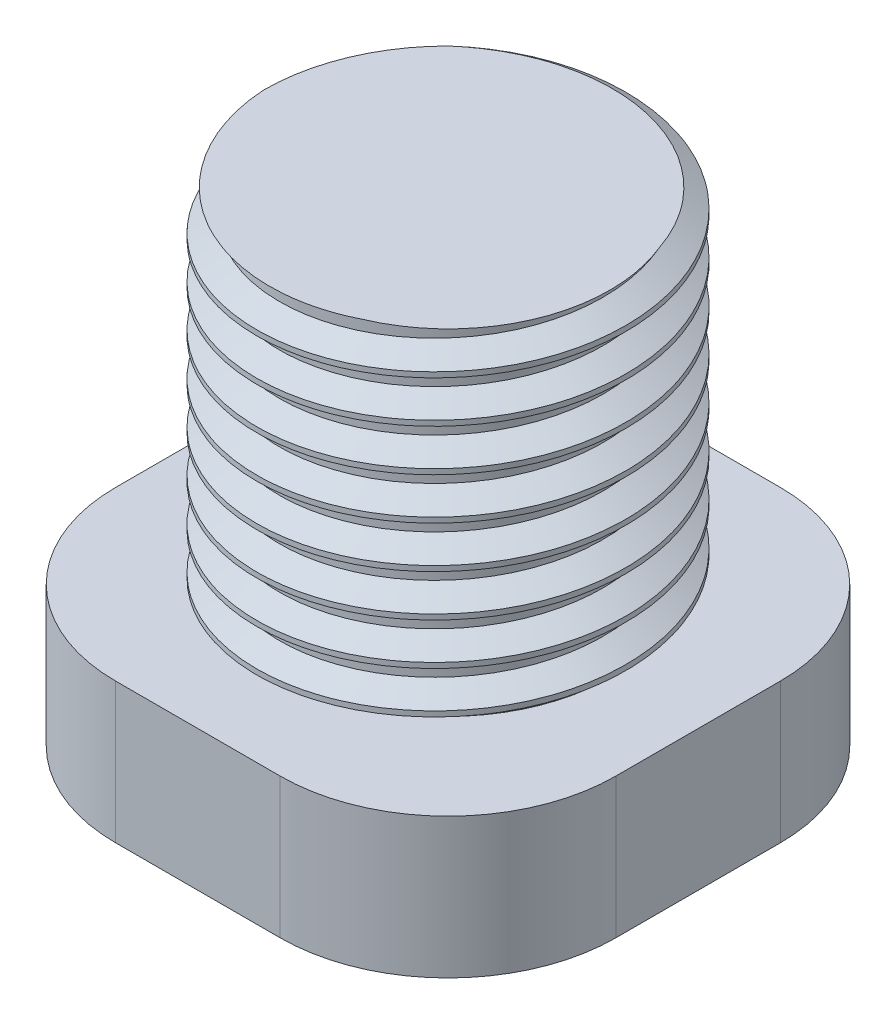
SolidWorks part; units mm, degrees
ref_plane "Front Plane" through (0, 0, 0) normal (0, 0, 1) x (1, 0, 0)
ref_plane "Top Plane" through (0, 0, 0) normal (0, 1, 0) x (1, 0, 0)
ref_plane "Right Plane" through (0, 0, 0) normal (1, 0, 0) x (0, 0, -1)
sketch "Sketch2" plane through (0, 0, 0) normal (0, 1, 0) x (1, 0, 0)
  circle A0 centre (0, 0) radius 11
  dimension "D1" = 22
extrude "Boss-Extrude1" add sketch "Sketch2" along normal blind 20
sketch "Sketch35" plane through (0, 0, 0) normal (0, 1, 0) x (1, 0, 0)
  line L0 (-14.9, -14.9) -> (-14.9, 14.9)
  line L1 (-15, -15) -> (15, -15)
  line L2 (-15, -15) -> (-15, 15)
  line L3 (-15, 15) -> (15, 15)
  line L4 (15, -15) -> (15, 15)
  line L5 (-15, -15) -> (15, 15) construction
  line L6 (-15, 15) -> (15, -15) construction
  line L7 (-14.9, 14.9) -> (14.9, 14.9)
  line L8 (14.9, -14.9) -> (14.9, 14.9)
  line L9 (-14.9, -14.9) -> (14.9, -14.9)
  point P0 (0, 0)
  dimension "D1" = 30
  dimension "D2" = 30
  dimension "D3" = 0.1
extrude "Boss-Extrude2" add sketch "Sketch35" against normal blind 8.35 contours L0 L9 L8 L7 region at (0, 0, 0)
thread "Thread3" pitch 2.5 method cut trim with end face yes profile "Thread Profile3" start angle 0, offset 5, length 0, pitch 2.5, diameter 22
ref_plane "Plane3" through (-11, 25, 0) normal (0, 0, 1) x (-1, 0, 0)
sketch "Thread Profile3" plane through (-11, 25, 0) normal (0, 0, 1) x (-1, 0, 0)
  line L0 (0, 0) -> (0, 2.5) construction
  line L11 (0, 0) -> (0, 2.1875)
  line L12 (0, 2.1875) -> (-1.3532, 1.4062)
  line L13 (-1.3532, 1.4062) -> (-1.3532, 0.7812)
  line L15 (-1.3532, 0.7812) -> (0, 0)
  line L17 (-1.3532, 1.0937) -> (0, 1.0937) construction
  point P2 (0, 0)
  dimension "Pitch" = 2.5
  dimension "Profile_Angle" = 60
  dimension "Profile_Land" = 0.625
  dimension "Profile_Height" = 1.3532
fillet "Fillet1" radius 10 4 edges at (14.9, -4.175, 14.9) (-14.9, -4.175, 14.9) (-14.9, -4.175, -14.9) (14.9, -4.175, -14.9)
sketch "Sketch36" plane through (0, -8.35, 0) normal (0, -1, 0) x (1, 0, 0)
  circle A0 centre (0, 0) radius 2.125
  dimension "D1" = 4.25
extrude "Cut-Extrude1" cut sketch "Sketch36" against normal blind 5 contours A0 region at (0, -8.35, 0)
